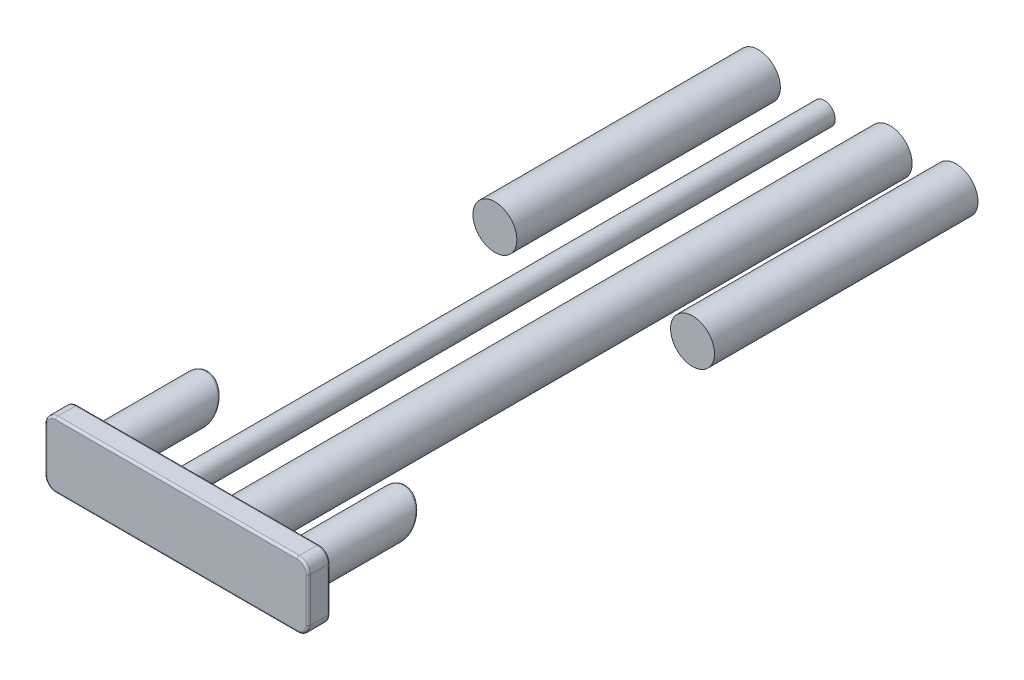
SolidWorks part; units mm, degrees
ref_plane "Front Plane" through (0, 0, 0) normal (0, 0, 1) x (1, 0, 0)
ref_plane "Top Plane" through (0, 0, 0) normal (0, 1, 0) x (1, 0, 0)
ref_plane "Right Plane" through (0, 0, 0) normal (1, 0, 0) x (0, 0, -1)
sketch "Sketch1" plane through (0, 0, 0) normal (0, 0, 1) x (1, 0, 0)
  line L0 (55, 0) -> (-55, 0) construction
  line L1 (0, -55) -> (0, 55) construction
  circle A0 centre (-0.75, 0) radius 0.25
  circle A1 centre (0.75, 0) radius 0.5
  circle A2 centre (2.25, 0) radius 0.5
  circle A3 centre (-2.25, 0) radius 0.5
  dimension "D1" = 1
  dimension "D2" = 0.5
  dimension "D3" = 0.75
  dimension "D4" = 1
  dimension "D6" = 1
  dimension "D5" = 0.75
  dimension "D7" = 1.5
  dimension "D8" = 1.5
extrude "Boss-Extrude1" add sketch "Sketch1" along normal blind 15
sketch "Sketch2" plane through (0, 0, 15) normal (0, 0, 1) x (1, 0, 0)
  circle A0 centre (0.75, 0) radius 0.25
  dimension "D1" = 0.5
extrude "Cut-Extrude1" cut sketch "Sketch2" against normal blind 12
sketch "Sketch3" plane through (0, 0, 15) normal (0, 0, 1) x (1, 0, 0)
  circle A0 centre (-2.25, 0) radius 0.7972
  circle A1 centre (2.25, 0) radius 0.8053
extrude "Cut-Extrude2" cut sketch "Sketch3" against normal blind 9
sketch "Sketch4" plane through (0, 0, 15) normal (0, 0, 1) x (1, 0, 0)
  line L0 (3.3564, 0) -> (-3.3564, 0) construction
  line L1 (-3, 0.75) -> (3, 0.75)
  line L2 (-3, 0.75) -> (-3, -0.75)
  line L3 (-3, -0.75) -> (3, -0.75)
  line L4 (3, 0.75) -> (3, -0.75)
  line L5 (0, -0.8859) -> (0, 0.8859) construction
  dimension "D1" = 0.75
  dimension "D2" = 0.75
  dimension "D3" = 3
  dimension "D4" = 3
extrude "Boss-Extrude2" add sketch "Sketch4" along normal blind 0.5
sketch "Sketch5" plane through (0, 0, 15) normal (0, 0, -1) x (-1, 0, 0)
  line L0 (-3, 0.75) -> (3, 0.75) construction
  circle A0 centre (2.25, 0) radius 0.45
  circle A1 centre (-2.25, 0) radius 0.45
  circle A2 centre (-0.75, 0) radius 0.5 construction
  circle A3 centre (0.75, 0) radius 0.25 construction
  dimension "D4" = 1.5
  dimension "D5" = 0.9
  dimension "D6" = 0.9
  dimension "D1" = 1.5
  dimension "D2" = 0.75
  dimension "D3" = 0.75
extrude "Boss-Extrude3" add sketch "Sketch5" along normal blind 2.5
sketch "Sketch6" plane through (0, 0, 0) normal (1, 0, 0) x (0, 0, -1)
  line L3 (-12.5, 0.45) -> (-12.5, -0.45)
  line L4 (-12.5, 0.45) -> (-13, -0.45)
  line L5 (-15, -0.45) -> (-12.5, -0.45) construction
  line L6 (-13, -0.45) -> (-12.5, -0.45)
extrude "Cut-Extrude3" cut sketch "Sketch6" against normal blind 2.5 from offset 1.5 offset against normal yes
sketch "Sketch7" plane through (0, 0, 0) normal (1, 0, 0) x (0, 0, -1)
  line L0 (-12.5, 0.45) -> (-13, -0.45)
  line L1 (-15, -0.45) -> (-12.5, -0.45) construction
  line L2 (-13, -0.45) -> (-12.5, -0.45)
  line L3 (-12.5, -0.45) -> (-12.5, 0.45)
  dimension "D1" = 0.5
extrude "Cut-Extrude5" cut sketch "Sketch7" along normal blind 2.5 from offset 1.5
fillet "Fillet1" radius 0.25 4 edges at (-3, -0.75, 15.25) (-3, 0.75, 15.25) (3, -0.75, 15.25) (3, 0.75, 15.25)
fillet "Fillet2" radius 0.05 22 edges at (-2.9268, 0.6768, 15.5) (0, 0.75, 15.5) (2.9268, 0.6768, 15.5) (3, 0, 15.5) (2.9268, -0.6768, 15.5) (0, -0.75, 15.5) (-2.9268, -0.6768, 15.5) (-3, 0, 15.5) (2.7, 0, 15) (1.25, 0, 15) (2.9268, -0.6768, 15) (3, 0, 15) (2.9268, 0.6768, 15) (0, 0.75, 15) (-2.9268, 0.6768, 15) (-3, 0, 15) (-2.9268, -0.6768, 15) (0, -0.75, 15) (-0.5, 0, 15) (-1.8, 0, 15) (-2.25, -0.45, 13) (2.25, -0.45, 13)
